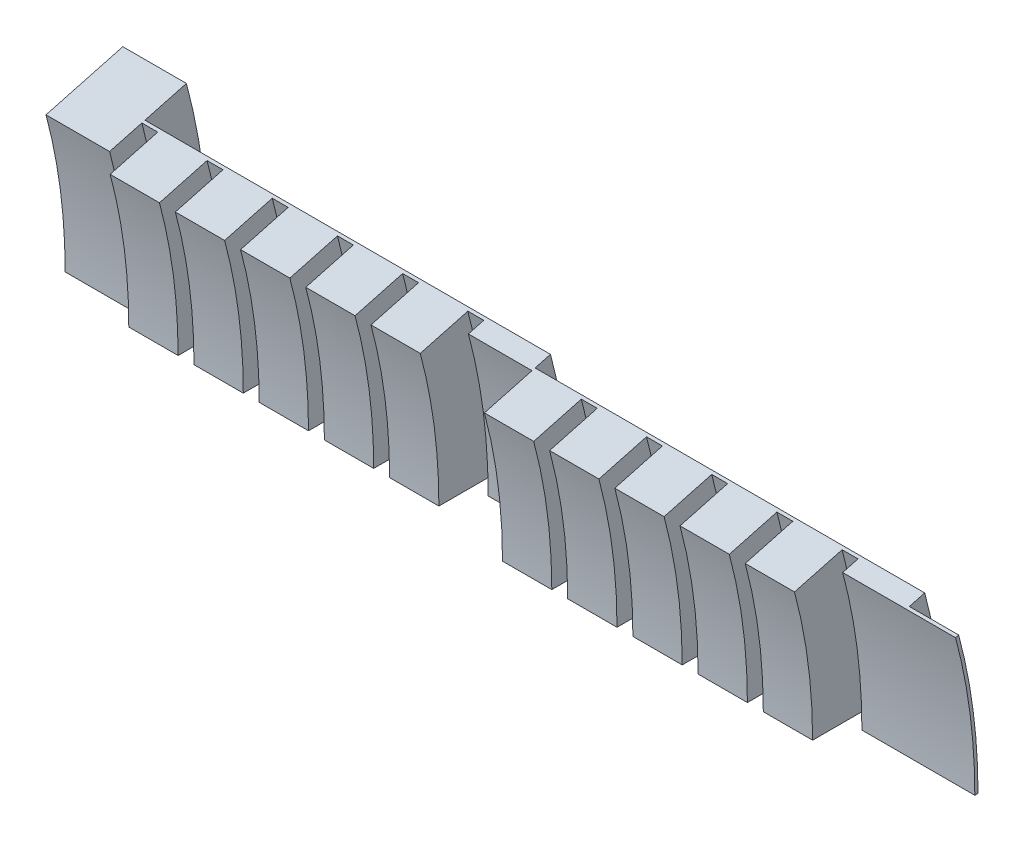
SolidWorks part; units mm, degrees
ref_plane "Front Plane" through (0, 0, 0) normal (0, 0, 1) x (1, 0, 0)
ref_plane "Top Plane" through (0, 0, 0) normal (0, 1, 0) x (1, 0, 0)
ref_plane "Right Plane" through (0, 0, 0) normal (1, 0, 0) x (0, 0, -1)
sketch "Sketch1" plane through (0, 0, 0) normal (0, 1, 0) x (1, 0, 0)
  line L0 (0, 0) -> (6.3693, 0) construction
  line L1 (0.254, 9.525) -> (0.254, 8.7376)
  line L2 (0.254, 8.7376) -> (1.0414, 8.7376)
  line L3 (1.0414, 8.7376) -> (1.0414, 9.525)
  line L4 (1.0414, 9.525) -> (1.2954, 9.525)
  line L5 (1.2954, 9.525) -> (1.2954, 8.7376)
  line L6 (1.2954, 8.7376) -> (2.0828, 8.7376)
  line L7 (2.0828, 8.7376) -> (2.0828, 9.525)
  line L8 (2.0828, 9.525) -> (2.3368, 9.525)
  line L9 (2.3368, 9.525) -> (2.3368, 8.7376)
  line L10 (2.3368, 8.7376) -> (3.1242, 8.7376)
  line L11 (3.1242, 8.7376) -> (3.1242, 9.525)
  line L12 (3.1242, 9.525) -> (3.3782, 9.525)
  line L13 (3.3782, 9.525) -> (3.3782, 8.7376)
  line L14 (3.3782, 8.7376) -> (4.1656, 8.7376)
  line L15 (4.1656, 8.7376) -> (4.1656, 9.525)
  line L16 (4.1656, 9.525) -> (4.4196, 9.525)
  line L17 (4.4196, 9.525) -> (4.4196, 8.7376)
  line L18 (4.4196, 8.7376) -> (5.207, 8.7376)
  line L19 (5.207, 8.7376) -> (5.207, 9.525)
  line L20 (5.207, 9.525) -> (5.461, 9.525)
  line L21 (5.461, 9.525) -> (5.461, 9.271)
  line L22 (5.461, 9.271) -> (6.477, 9.271)
  line L23 (6.477, 9.271) -> (6.477, 8.4836)
  line L24 (6.477, 8.4836) -> (7.2644, 8.4836)
  line L25 (7.2644, 8.4836) -> (7.2644, 9.271)
  line L26 (7.2644, 9.271) -> (7.5184, 9.271)
  line L27 (7.5184, 9.271) -> (7.5184, 8.4836)
  line L28 (7.5184, 8.4836) -> (8.3058, 8.4836)
  line L29 (8.3058, 8.4836) -> (8.3058, 9.271)
  line L30 (8.3058, 9.271) -> (8.5598, 9.271)
  line L31 (8.5598, 9.271) -> (8.5598, 8.4836)
  line L32 (8.5598, 8.4836) -> (9.3472, 8.4836)
  line L33 (9.3472, 8.4836) -> (9.3472, 9.271)
  line L34 (9.3472, 9.271) -> (9.6012, 9.271)
  line L35 (9.6012, 9.271) -> (9.6012, 8.4836)
  line L36 (9.6012, 8.4836) -> (10.3886, 8.4836)
  line L37 (10.3886, 8.4836) -> (10.3886, 9.271)
  line L38 (10.3886, 9.271) -> (10.6426, 9.271)
  line L39 (10.6426, 9.271) -> (10.6426, 8.4836)
  line L40 (10.6426, 8.4836) -> (11.43, 8.4836)
  line L41 (11.43, 8.4836) -> (11.43, 9.271)
  line L42 (11.43, 9.271) -> (11.684, 9.271)
  line L43 (11.684, 9.271) -> (11.684, 9.017)
  line L44 (11.684, 9.017) -> (12.7, 9.017)
  line L131 (0.254, 9.525) -> (0, 9.525)
  line L132 (0, 0) -> (0, 9.525) construction
  line L139 (6.477, 9.5758) -> (6.477, 9.3218)
  line L145 (12.7, 9.3218) -> (12.7, 9.0678)
  line L166 (0, 9.525) -> (0, 8.9916)
  line L167 (0, 8.9916) -> (-1.016, 8.9916)
  line L168 (-1.016, 8.9916) -> (-1.016, 10.2616)
  line L169 (6.477, 9.3218) -> (12.7, 9.3218)
  line L170 (6.477, 9.5758) -> (0, 9.5758)
  line L171 (-1.016, 10.2616) -> (0, 10.2616)
  line L172 (0, 10.2616) -> (0, 9.5758)
  line L173 (12.7, 9.0678) -> (13.4874, 9.0678)
  line L174 (13.4874, 9.0678) -> (13.4874, 9.017)
  line L175 (13.4874, 9.017) -> (12.7, 9.017)
  dimension "D1" = 0.254
  dimension "D2" = 0.7874
  dimension "D3" = 0.7874
  dimension "D4" = 1.016
  dimension "D5" = 0.254
  dimension "D6" = 9.525
  dimension "D9" = 1.27
  dimension "D10" = 0.254
  dimension "D11" = 1.016
  dimension "D12" = 0.254
  dimension "D16" = 0.7874
revolve "Revolve1" add sketch "Sketch1" angle 15 about L0
ref_plane "Plane1" through (0, 0, 0) normal (0, -0.9914, -0.1305) x (-1, 0, 0)
ref_plane "Plane2" through (0, 1.2499, -9.4939) normal (0, 0.1305, -0.9914) x (-1, 0, 0)
ref_plane "Plane3" through (0, 1.2167, -9.2421) normal (0, 0.1305, -0.9914) x (-1, 0, 0)
